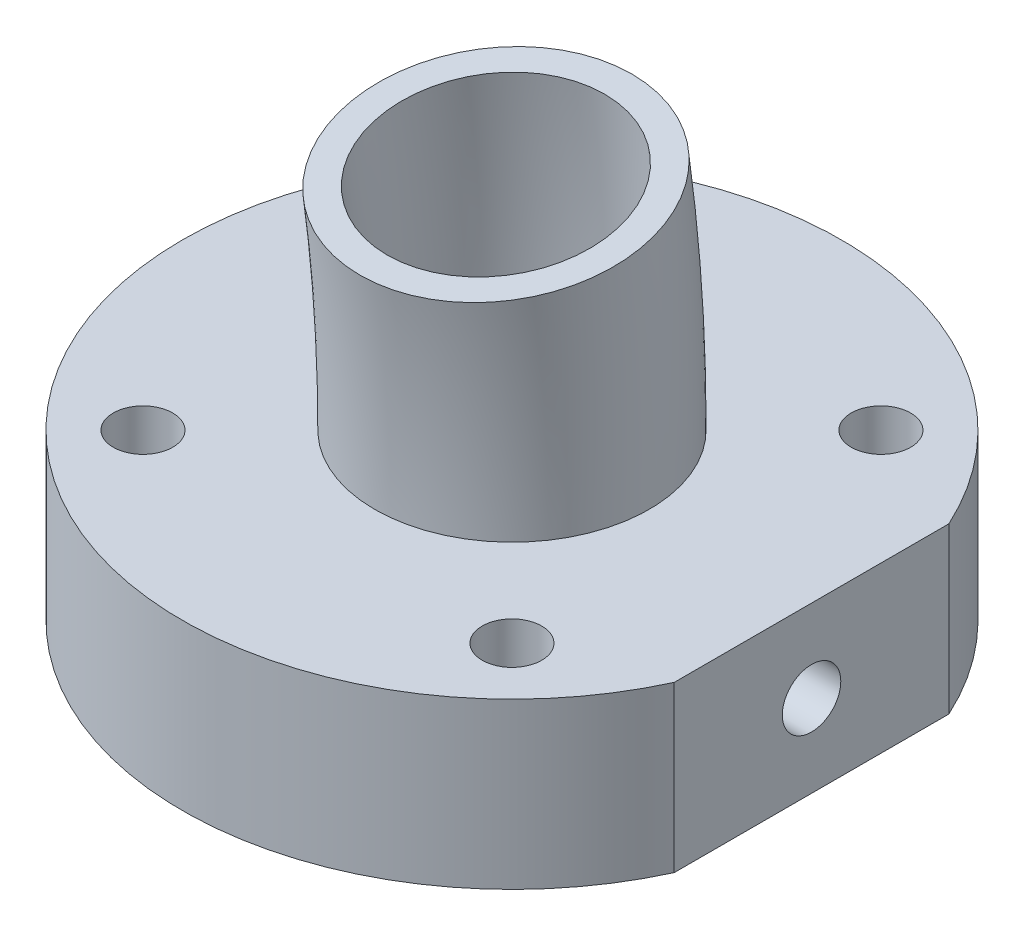
SolidWorks part; units mm, degrees
material "PMMA"
ref_plane "Front Plane" through (0, 0, 0) normal (0, 0, 1) x (1, 0, 0)
ref_plane "Top Plane" through (0, 0, 0) normal (0, 1, 0) x (1, 0, 0)
ref_plane "Right Plane" through (0, 0, 0) normal (1, 0, 0) x (0, 0, -1)
sketch "Sketch1" plane through (0, 0, 0) normal (0, 1, 0) x (1, 0, 0)
  circle A0 centre (0, 0) radius 30.48
extrude "Main Body Extrude" add sketch "Sketch1" along normal blind 15.24
sketch "Sketch2" plane through (0, 15.24, 0) normal (0, 1, 0) x (1, 0, 0)
  circle A0 centre (0, 0) radius 10.16
  dimension "D1" = 20.32
extrude "Through Hole For Blood" cut sketch "Sketch2" against normal through all both and the other way through all contours A0
sketch "Sketch18" plane through (0, 0, 0) normal (0, -1, 0) x (-1, 0, 0)
  line L0 (-21.7412, 7.0641) -> (0, 0) construction
  line L1 (0, 0) -> (0, 7.2573) construction
  circle A0 centre (-21.7412, 7.0641) radius 2.5908
  dimension "D2" = 22.86
  dimension "D1" = 5.1816
  dimension "D3" = 72
extrude "Alignment Dowel" [suppressed] add sketch "Sketch18" along normal blind 3.81
pattern_circular "Dowel Pattern" [suppressed] count 2 over 360 of bodies 153
sketch "Sketch27" plane through (0, 0, 0) normal (0, -1, 0) x (1, 0, 0)
  line L0 (0, 0) -> (0, 22.86) construction
  circle A1 centre (0, 22.86) radius 2.54
  dimension "D1" = 5.08
  dimension "D2" = 22.86
extrude "Dowel Hole" [suppressed] cut sketch "Sketch27" against normal blind 3.81
pattern_circular "Dowel Hole Pattern" [suppressed] count 2 over 360 of bodies 158
sketch "Sketch40" plane through (0, 0, 0) normal (0, -1, 0) x (-1, 0, 0)
  line L0 (0, 0) -> (17.0625, -17.0625) construction
  line L2 (0, 0) -> (30.48, 0) construction
  circle A0 centre (0, 0) radius 30.48 construction
  point P0 (17.0625, -17.0625)
  dimension "D1" = 24.13
  dimension "D2" = 45
hole_wizard "M5 Clearance Hole" positions "Sketch40" profile "Sketch39" hole size "M5" standard "ANSI Metric" end condition through all
sketch "Sketch39" plane through (-17.0625, 0, 17.0625) normal (1, 0, 0) x (0, 0, -1)
  line L0 (0, 0) -> (0, 15.24)
  line L1 (0, 15.24) -> (2.75, 15.24)
  line L2 (2.75, 15.24) -> (2.75, 0)
  line L5 (2.75, 0) -> (0, 0)
  line L11 (0, -6.35) -> (0, 107.95) construction
  dimension "Thru Hole Dia." = 5.5
  dimension "Thru Hole Depth" = 15.24
pattern_circular "Screw Hole Pattern" count 4 over 360 about axis through (0, 0, 0) along (0, 1, 0) of "M5 Clearance Hole"
sketch "Sketch42" plane through (0, 0, 0) normal (0, -1, 0) x (1, 0, 0)
  line L1 (27.7081, 12.7) -> (27.7081, -12.7)
  circle A2 centre (0, 0) radius 30.48 construction
  arc A3 (27.7081, -12.7) -> (27.7081, 12.7) centre (0, 0) ccw
  point P0 (27.7081, 0)
  dimension "D1" = 25.4
extrude "Cut-Extrude2" cut sketch "Sketch42" against normal through all
sketch "Sketch43" plane through (27.7081, 0, 0) normal (1, 0, 0) x (0, 0, -1)
  line L0 (12.7, 15.24) -> (12.7, 0) construction
  circle A0 centre (0, 6.35) radius 3.525
  dimension "D1" = 7.05
  dimension "D2" = 12.7
  dimension "D3" = 6.35
sketch "Sketch48" [suppressed] plane through (0, 0, 0) normal (0, 0, 1) x (1, 0, 0)
  line L0 (-30.48, 0) -> (27.7081, 0) construction
  line L1 (16.3703, 0) -> (19.0373, 0)
  line L2 (16.3703, 0) -> (16.3703, 1.2446)
  line L3 (16.3703, 1.2446) -> (19.0373, 1.2446)
  line L4 (19.0373, 0) -> (19.0373, 1.2446)
  line L5 (0, 0) -> (0, 15.24) construction
  line L6 (27.7081, 15.24) -> (-30.48, 15.24) construction
  dimension "D1" = 19.0373
  dimension "D2" = 1.2446
  dimension "D3" = 2.667
revolve "Cut-Revolve1" [suppressed] cut sketch "Sketch48" angle 360 about L5
extrude "Flat Side Dowel Hole" cut sketch "Sketch18<7>" against normal blind 3.81
sketch "Sketch18<7>" plane through (0, 0, 0) normal (0, -1, 0) x (-1, 0, 0) same geometry as "Sketch18"
extrude "Flat Side Dowel" add sketch "Sketch27<4>" along normal blind 3.81
sketch "Sketch27<4>" plane through (0, 0, 0) normal (0, -1, 0) x (1, 0, 0) same geometry as "Sketch27"
pattern_circular "CirPattern1" count 2 over 360 about axis through (0, 0, 0) along (0, 1, 0) of "Flat Side Dowel Hole"
pattern_circular "CirPattern2" count 2 over 360 about axis through (0, 0, 0) along (0, 1, 0) of "Flat Side Dowel"
sketch "Sketch51" plane through (0, 15.24, 0) normal (0, 1, 0) x (1, 0, 0)
  line L1 (0, 152.4) -> (-35.5894, 152.4) construction
  line L2 (27.7081, -12.7) -> (27.7081, 12.7) construction
  circle A0 centre (0, 0) radius 12.7
  circle A1 centre (0, 0) radius 10.16
  dimension "D1" = 25.4
  dimension "D2" = 20.32
  dimension "D3" = 152.4
revolve "Revolve1" [suppressed] add sketch "Sketch51" angle 8 about L1
sketch "Sketch52" plane through (0, 15.24, 0) normal (0, 1, 0) x (1, 0, 0)
  line L0 (0, -152.4) -> (-73.1164, -152.4) construction
  circle A0 centre (0, 0) radius 10.16
  circle A1 centre (0, 0) radius 12.7
  dimension "D1" = 20.32
  dimension "D2" = 25.4
  dimension "D3" = 152.4
revolve "Revolve2" add sketch "Sketch52" angle 8 about L0 reverse direction yes
sketch "Sketch56" plane through (27.7081, 0, 0) normal (1, 0, 0) x (0, 0, -1)
  line L0 (-12.7, 15.24) -> (12.7, 15.24) construction
  line L1 (-12.7, 15.24) -> (-12.7, 0) construction
  point P0 (0, 7.62)
  dimension "D1" = 7.62
  dimension "D2" = 12.7
hole_wizard "1/4-28 Tapped Hole1" positions "Sketch56" profile "Sketch55" tap size "1/4-28" standard "ANSI Inch" end condition up to next
cosmetic thread "Hole Thread1"
sketch "Sketch55" plane through (27.7081, 7.62, 0) normal (0, 1, 0) x (0, 0, -1)
  line L0 (0, 0) -> (0, 17.5481)
  line L1 (0, 17.5481) -> (2.7051, 17.5481)
  line L2 (2.7051, 17.5481) -> (2.7051, 0)
  line L5 (2.7051, 0) -> (0, 0)
  line L11 (0, -6.35) -> (0, 107.95) construction
  dimension "Thru Tap Drill Dia." = 5.4102
  dimension "Thru Tap Drill Depth" = 17.5481
equation "\"Dowel Distance\"= .9in"
equation "\"Hole Distance\"=0.95"
equation "\"D2@Sketch27\"=\"Dowel Distance\""
equation "\"D1@Sketch40\"=\"Hole Distance\""
equation "\"Body OD\"= 2.40in"
equation "\"Blood Flow Hole\"= .8in"
equation "\"D1@Sketch2\"=\"Blood Flow Hole\""
equation "\"D1@Sketch1\"=\"Body OD\""
equation "\"D2@Sketch18\"=\"Dowel Distance\""
